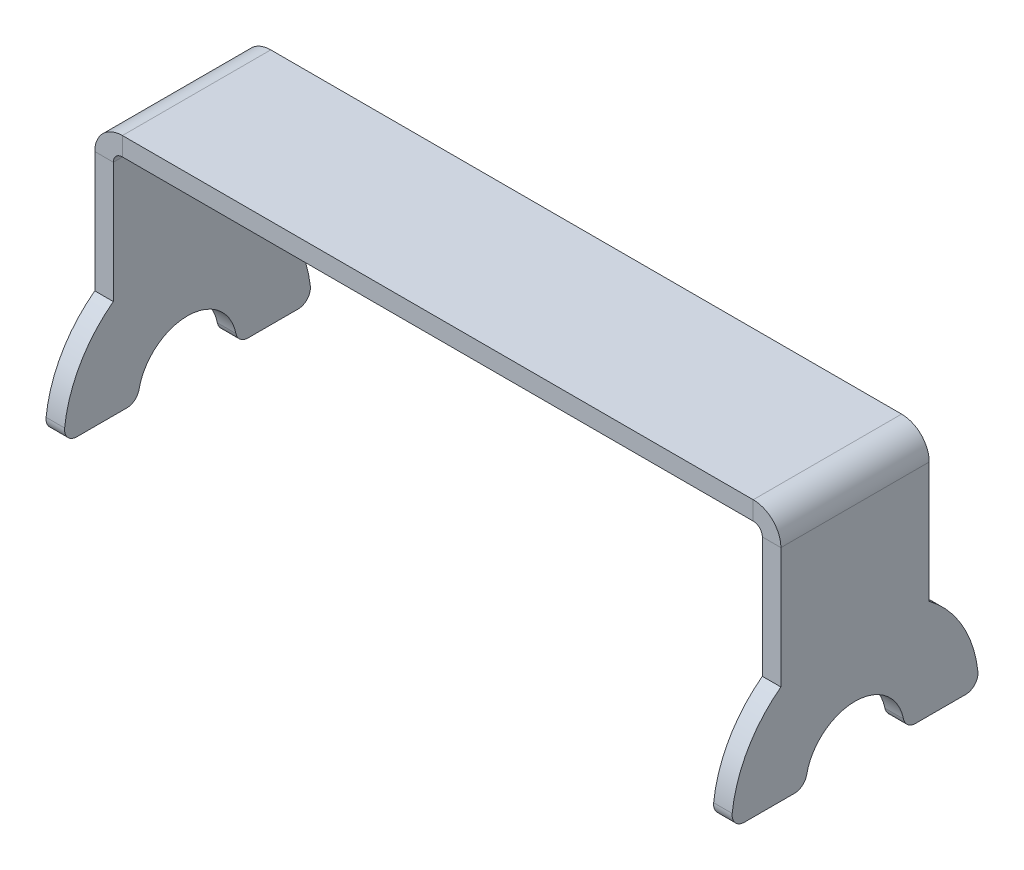
SolidWorks part; units mm, degrees
note: The reader was unsure of these and kept them because the rebuilt part matched: flange length of "Brida de arista1".
ref_plane "Alzado" through (0, 0, 0) normal (0, 0, 1) x (1, 0, 0)
ref_plane "Planta" through (0, 0, 0) normal (0, 1, 0) x (1, 0, 0)
ref_plane "Vista lateral" through (0, 0, 0) normal (1, 0, 0) x (0, 0, -1)
sketch "Croquis2" plane through (0, 0, 0) normal (0, 1, 0) x (1, 0, 0)
  line L1 (-27.75, -6) -> (27.75, -6)
  line L2 (-27.75, -6) -> (-27.75, 6)
  line L3 (-27.75, 6) -> (27.75, 6)
  line L4 (27.75, -6) -> (27.75, 6)
  line L5 (-27.75, -6) -> (27.75, 6) construction
  line L6 (-27.75, 6) -> (27.75, -6) construction
  point P0 (0, 0)
  dimension "D1" = 55.5
  dimension "D2" = 12
base flange "Brida base1" sketch "Croquis2" thickness 1.5 reverse thickness direction no parameters "D1"=0.7366
edge flange "Brida de arista1" sketch "Croquis11" flange profiles "Croquis11", "Croquis12" flange angle 90 flange length 20 flange position material inside bend radius 0.7366 thickness 1.5 parameters "D6"=10, "D8"=0.5
sketch "Croquis11" plane through (-27.75, -1.5, 0) normal (-1, 0, 0) x (0, 0, -1)
  line L2 (-6, 0) -> (-6, 18.5)
  line L3 (-6, 18.5) -> (6, 18.5)
  line L4 (6, 18.5) -> (6, 0)
  line L5 (6, 0) -> (-6, 0) construction
  line L6 (6, 0) -> (-6, 0)
sketch "Croquis12" plane through (27.75, -1.5, 0) normal (1, 0, 0) x (0, 0, 1)
  line L0 (6, 0) -> (-6, 0) construction
  line L1 (6, 0) -> (-6, 0)
  line L2 (-6, 0) -> (-6, 18.5)
  line L3 (-6, 18.5) -> (6, 18.5)
  line L4 (6, 18.5) -> (6, 0)
bend "Pliegue de arista1" bend radius 0.7366 bend angle 90 parameters "D5"=1
bend "Pliegue de arista2" bend radius 0.7366 bend angle 90 parameters "D5"=2
sketch "Croquis13" plane through (-27.75, 0, 0) normal (-1, 0, 0) x (0, 0, 1)
  line L0 (-5.0937, -11.3945) -> (5.3225, -11.3945) construction
  line L1 (-6, -20) -> (-10, -20)
  line L2 (-6, -20) -> (-6, -12)
  line L6 (0, -20) -> (0, -17.8238) construction
  line L7 (6, -20) -> (10, -20)
  line L8 (6, -20) -> (6, -12)
  line L11 (-6, -20) -> (6, -20) construction
  arc A0 (-6, -12) -> (-10, -20) centre (0, -20) ccw
  arc A1 (10, -20) -> (6, -12) centre (0, -20) ccw
  dimension "D3" = 20
extrude "Saliente-Extruir1" add sketch "Croquis13" against normal up to surface (1.5 mm away) up to face at (-26.25, -11.1183, 0)
sketch "Croquis16" plane through (27.75, 0, 0) normal (1, 0, 0) x (0, 0, -1)
  line L0 (-6, -20) -> (6, -20) construction
  line L1 (-10, -20) -> (-6, -20)
  line L2 (-6, -20) -> (-6, -12)
  line L4 (6, -20) -> (10, -20)
  line L5 (6, -20) -> (6, -12)
  arc A0 (-6, -12) -> (-10, -20) centre (0, -20) ccw
  arc A1 (10, -20) -> (6, -12) centre (0, -20) ccw
extrude "Saliente-Extruir2" add sketch "Croquis16" against normal up to surface (1.5 mm away) up to face at (26.25, -11.1183, 0)
sketch "Croquis17" plane through (-27.75, 0, 0) normal (-1, 0, 0) x (0, 0, 1)
  line L0 (0, -20) -> (0, -18) construction
  line L1 (-10, -20) -> (10, -20) construction
  circle A0 centre (0, -20) radius 4
  dimension "D2" = 8
  dimension "D1" = 2
extrude "Cortar-Extruir2" cut sketch "Croquis17" against normal up to surface (55.5 mm away) up to face at (27.75, -11.2548, 0)
fillet "Redondeo1" radius 1 4 edges at (27, -20, -10) (27, -20, 10) (27, -20, 4) (27, -20, -4)
fillet "Redondeo2" radius 1 4 edges at (-27, -20, -4) (-27, -20, 4) (-27, -20, -10) (-27, -20, 10)
sketch "Líneas de pliegue1" [suppressed] plane through (0, 0, 0) normal (0, 1, 0) x (1, 0, 0)
sketch "Cuadro delimitador1" [suppressed] plane through (0, 0, 0) normal (0, 1, 0) x (1, 0, 0)
sheet metal parameters "Chapa metálica2" thickness 1.5 parameters "D1"=0.7366
flat pattern "Chapa desplegada2" [suppressed]
sketch "Líneas de pliegue2" plane through (0, 0, 0) normal (0, 1, 0) x (1, 0, 0)
sketch3d "Cuadro delimitador2" [suppressed]
  line L0 (-22, 10, 0) -> (22, 10, 0) construction
  line L1 (-22, -10, 0) -> (22, -10, 0) construction
  line L2 (-22, 10, 0) -> (-22, -10, 0) construction
  line L3 (22, 10, 0) -> (22, -10, 0) construction
sheet metal parameters "Chapa metálica3" thickness 1.5 parameters "D1"=0.7366
flat pattern "Chapa desplegada2"
sketch "Líneas de pliegue2" plane through (0, 0, 0) normal (0, 1, 0) x (1, 0, 0)
  line L0 (26.681, -6) -> (26.681, 6) construction
  line L1 (-26.681, 6) -> (-26.681, -6) construction
  line L2 (26.681, -6) -> (26.681, 6) construction
  line L3 (-26.681, 6) -> (-26.681, -6) construction
sketch3d "Cuadro delimitador2" [suppressed]
  line L0 (45.6119, 6, 0) -> (-45.6119, 6, 0) construction
  line L1 (45.6119, -6, 0) -> (-45.6119, -6, 0) construction
  line L2 (45.6119, 6, 0) -> (45.6119, -6, 0) construction
  line L3 (-45.6119, 6, 0) -> (-45.6119, -6, 0) construction
bend of the flat pattern "Aplanar-<Pliegue de arista1>1"
bend of the flat pattern "Aplanar-<Pliegue de arista2>1"
sheet metal parameters "Chapa metálica5" thickness 1.5 parameters "D1"=0.7366
flat pattern "Chapa desplegada2" [suppressed]
sketch "Líneas de pliegue2" plane through (0, 0, 0) normal (0, 1, 0) x (1, 0, 0)
  line L0 (26.681, -6) -> (26.681, 6) construction
  line L1 (-26.681, 6) -> (-26.681, -6) construction
  line L2 (26.681, -6) -> (26.681, 6) construction
  line L3 (-26.681, 6) -> (-26.681, -6) construction
sketch3d "Cuadro delimitador2" [suppressed]
  line L0 (-45.6119, 10, 0) -> (45.6119, 10, 0) construction
  line L1 (-45.6119, -10, 0) -> (45.6119, -10, 0) construction
  line L2 (-45.6119, 10, 0) -> (-45.6119, -10, 0) construction
  line L3 (45.6119, 10, 0) -> (45.6119, -10, 0) construction
bend of the flat pattern "Aplanar-<Pliegue de arista1>1"
bend of the flat pattern "Aplanar-<Pliegue de arista2>1"
sketch "Croquis14-1" [suppressed] plane through (-25.6119, 0, 0) normal (0, 1, 0) x (0, 0, 1)
  line L0 (0, -20) -> (0, -18) construction
  circle A0 centre (0, -20) radius 4
  dimension "D2" = 8
  dimension "D1" = 2
sheet metal parameters "Chapa metálica7" thickness 1.5 parameters "D1"=0.7366
flat pattern "Chapa desplegada2"
sketch "Líneas de pliegue2" plane through (0, 0, 0) normal (0, 1, 0) x (1, 0, 0)
  line L0 (26.681, -6) -> (26.681, 6) construction
  line L1 (-26.681, 6) -> (-26.681, -6) construction
  line L2 (26.681, -6) -> (26.681, 6) construction
  line L3 (-26.681, 6) -> (-26.681, -6) construction
sketch3d "Cuadro delimitador2" [suppressed]
  line L0 (45.6119, 10, 0) -> (-45.6119, 10, 0) construction
  line L1 (45.6119, -10, 0) -> (-45.6119, -10, 0) construction
  line L2 (45.6119, 10, 0) -> (45.6119, -10, 0) construction
  line L3 (-45.6119, 10, 0) -> (-45.6119, -10, 0) construction
bend of the flat pattern "Aplanar-<Pliegue de arista1>1"
bend of the flat pattern "Aplanar-<Pliegue de arista2>1"
sheet metal parameters "Chapa metálica8" thickness 1.5 parameters "D1"=0.7366
flat pattern "Chapa desplegada2"
sketch "Líneas de pliegue2" plane through (0, 0, 0) normal (0, 1, 0) x (1, 0, 0)
  line L0 (26.681, -6) -> (26.681, 6) construction
  line L1 (-26.681, 6) -> (-26.681, -6) construction
  line L2 (26.681, -6) -> (26.681, 6) construction
  line L3 (-26.681, 6) -> (-26.681, -6) construction
sketch3d "Cuadro delimitador2" [suppressed]
  line L0 (45.6119, 9.9442, 0) -> (-45.6119, 9.9442, 0) construction
  line L1 (45.6119, -9.9438, 0) -> (-45.6119, -9.9438, 0) construction
  line L2 (45.6119, 9.9442, 0) -> (45.6119, -9.9438, 0) construction
  line L3 (-45.6119, 9.9442, 0) -> (-45.6119, -9.9438, 0) construction
bend of the flat pattern "Aplanar-<Pliegue de arista1>1"
bend of the flat pattern "Aplanar-<Pliegue de arista2>1"
